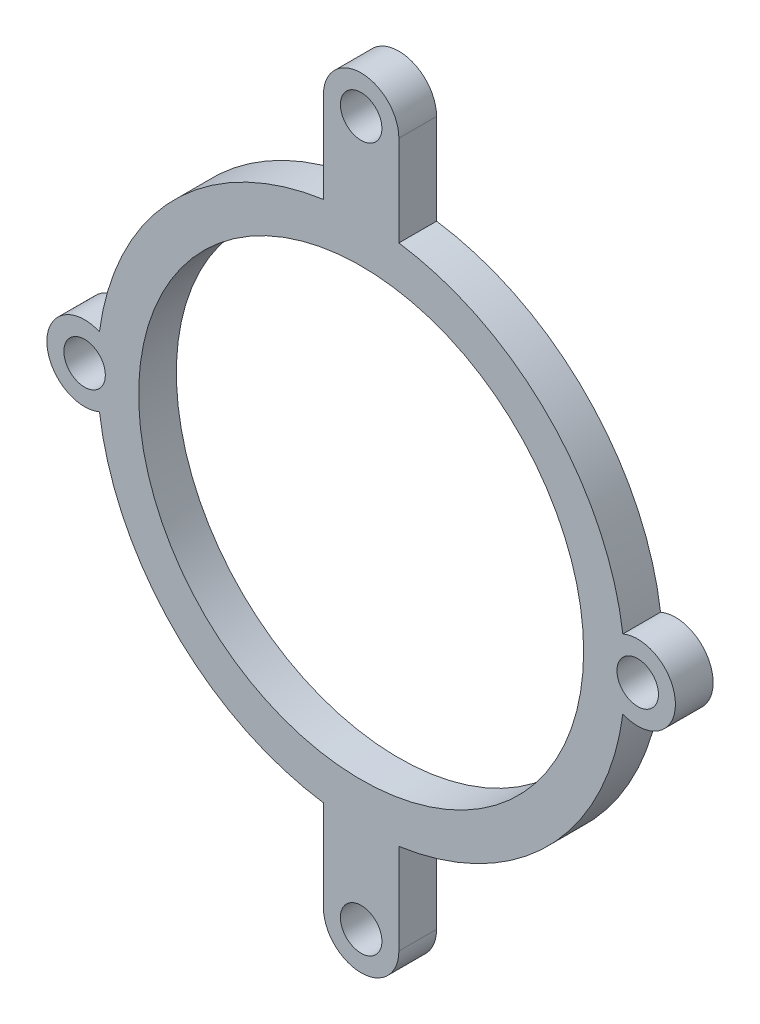
SolidWorks part; units mm, degrees
ref_plane "前视基准面" through (0, 0, 0) normal (0, 0, 1) x (1, 0, 0)
ref_plane "上视基准面" through (0, 0, 0) normal (0, 1, 0) x (1, 0, 0)
ref_plane "右视基准面" through (0, 0, 0) normal (1, 0, 0) x (0, 0, -1)
sketch "草图1" plane through (0, 0, 0) normal (0, 0, 1) x (1, 0, 0)
  line L4 (-3, 28) -> (-3, -28)
  line L5 (3, -28) -> (3, 28)
  line L6 (28, 3) -> (-28, 3)
  line L7 (-28, -3) -> (28, -3)
  circle A0 centre (0, 0) radius 17.7
  circle A1 centre (0, 28) radius 3
  circle A2 centre (0, 0) radius 21
  circle A3 centre (0, 28) radius 1.65
  circle A6 centre (0, -28) radius 1.65
  circle A7 centre (0, -28) radius 3
  circle A11 centre (-22, 0) radius 1.65
  circle A12 centre (22, 0) radius 1.65
  circle A13 centre (22, 0) radius 3
  circle A14 centre (-22, 0) radius 3
extrude "凸台-拉伸1" add sketch "草图1" along normal blind 3 contours L4 A2 L6 A0 | L5 A2 L4 A0 | L6 A2 L5 A0 | A2 L5 A1 L4 | A1 A3 | A13 A2 A12 | A13 A2 L6 A0 L7 | L5 A2 L7 A0 | A2 A13 A12 | A14 A2 L7 A0 L6 | L7 A2 L4 A0 | A2 A14 A11 | A2 A14 A11 | L4 A2 L5 A0 | A7 L5 A2 L4 | A7 A6 region at (0, 23.3332, 0) region at (0, 30.9151, 0) region at (0, 19.2714, 0) region at (-12.8333, 12.8333, 0) region at (12.8333, 12.8333, 0) region at (-18.6998, 0, 0) region at (18.6998, 0, 0) region at (-21.4115, 2.8671, 0) region at (-20.0365, 0, 0) region at (-12.8333, -12.8333, 0) region at (24.0696, 2.0696, 0) region at (20.0365, 0, 0) region at (0, -19.2714, 0) region at (0, -23.3332, 0) region at (12.8333, -12.8333, 0) region at (0, -25.0849, 0)
